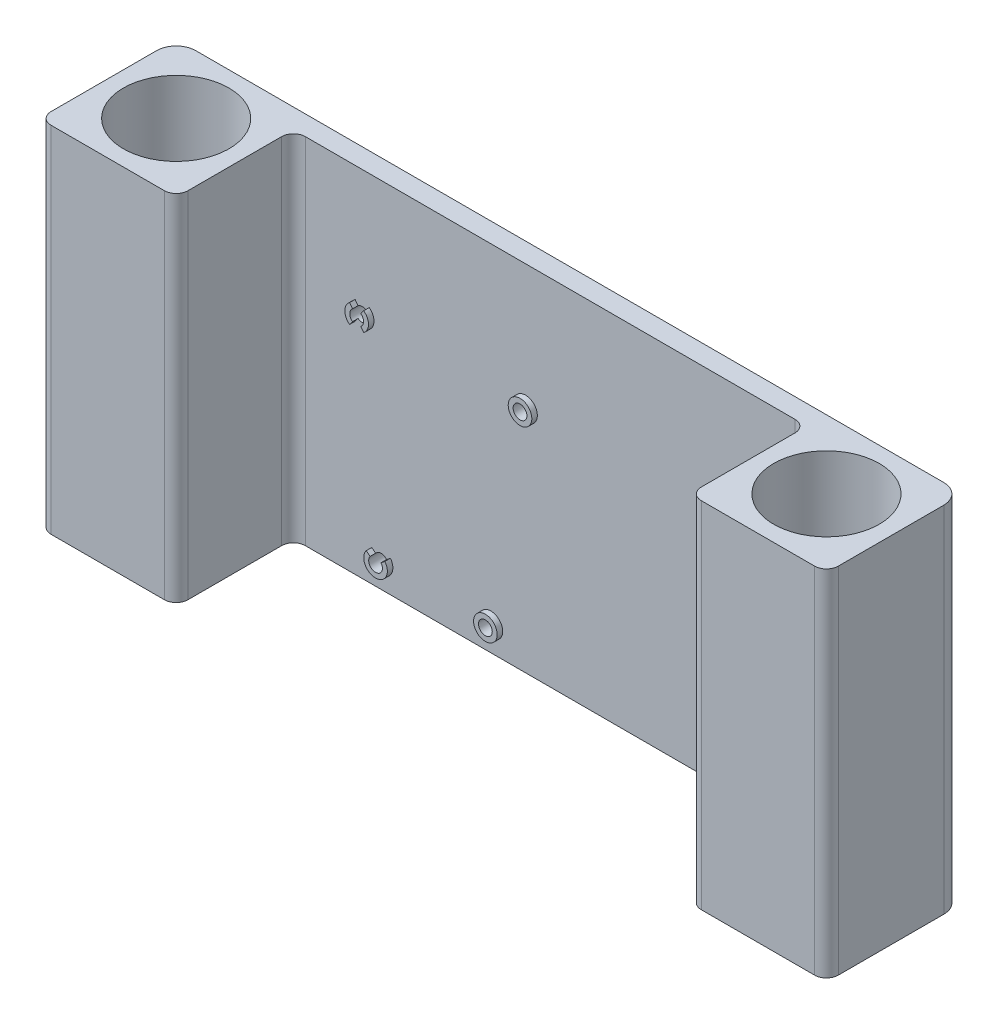
SolidWorks part; units mm, degrees
ref_plane "Front Plane" through (0, 0, 0) normal (0, 0, 1) x (1, 0, 0)
ref_plane "Top Plane" through (0, 0, 0) normal (0, 1, 0) x (1, 0, 0)
ref_plane "Right Plane" through (0, 0, 0) normal (1, 0, 0) x (0, 0, -1)
sketch "Sketch1" plane through (0, 0, 0) normal (0, 1, 0) x (1, 0, 0)
  line L1 (-17.4, 17.4) -> (17.4, 17.4)
  line L2 (-17.4, 17.4) -> (-17.4, -17.4)
  line L3 (-17.4, -17.4) -> (17.4, -17.4)
  line L4 (17.4, 12.4) -> (17.4, -17.4)
  line L5 (-17.4, 17.4) -> (17.4, -17.4) construction
  line L6 (-17.4, -17.4) -> (17.4, 17.4) construction
  line L11 (17.4, 17.4) -> (82.6, 17.4)
  line L13 (17.4, 12.4) -> (82.6, 12.4)
  line L14 (82.6, 17.4) -> (82.6, 12.4)
  circle A0 centre (0, 0) radius 13.4
  dimension "D1" = 26.8
  dimension "D2" = 34.8
  dimension "D3" = 34.8
  dimension "D4" = 5
extrude "Boss-Extrude1" add sketch "Sketch1" along normal blind 90 contours L14 L11 L4 L13 | L4 L1 L2 L3 A0 region at (16.7534, 0, -4.9925)
mirror "Mirror3" about plane through (82.6, 90, 0) normal (1, 0, 0) of "Boss-Extrude1"
fillet "Fillet1" radius 5 2 edges at (182.6, 45, -17.4) (-17.4, 45, -17.4)
fillet "Fillet2" radius 3 4 edges at (182.6, 45, 17.4) (147.8, 45, 17.4) (17.4, 45, 17.4) (-17.4, 45, 17.4)
fillet "Fillet3" radius 3 2 edges at (17.4, 45, -12.4) (147.8, 45, -12.4)
sketch "Sketch2" plane through (0, 0, -12.4) normal (0, 0, 1) x (1, 0, 0)
  line L1 (32.4, 4.7638) -> (32.4, 77.8661) construction
  line L3 (17.4, 0) -> (17.4, 90) construction
  circle A0 centre (39.65, 6.1978) radius 1.75
  circle A1 centre (67.55, 6.1978) radius 1.75
  circle A2 centre (34.85, 58.0978) radius 1.75
  circle A3 centre (76.35, 58.0978) radius 1.75
  point P8 (0, 0)
  point P9 (0, 0)
  point P10 (64.7447, 4.5183)
  point P11 (64.6447, 5.6176)
  point P12 (36.7447, 3.3545)
  point P13 (36.7447, 5.9964)
  point P14 (36.7447, 6.1978)
  dimension "D1" = 3.5
  dimension "D2" = 3.5
  dimension "D3" = 2.45
  dimension "D4" = 3.5
  dimension "D5" = 27.9
  dimension "D6" = 41.5
  dimension "D7" = 7.25
  dimension "D8" = 51.9
  dimension "D9" = 15
extrude "Cut-Extrude1" cut sketch "Sketch2" against normal blind 10
sketch "Sketch3" plane through (0, 0, -17.4) normal (0, 0, 1) x (1, 0, 0)
  line L13 (42.9409, 6.1978) -> (41.2954, 9.0478)
  line L14 (41.2954, 9.0478) -> (38.0046, 9.0478)
  line L15 (38.0046, 9.0478) -> (36.3591, 6.1978)
  line L16 (36.3591, 6.1978) -> (38.0046, 3.3478)
  line L17 (38.0046, 3.3478) -> (41.2954, 3.3478)
  line L18 (41.2954, 3.3478) -> (42.9409, 6.1978)
  line L19 (70.8409, 6.1978) -> (69.1954, 9.0478)
  line L20 (69.1954, 9.0478) -> (65.9046, 9.0478)
  line L21 (65.9046, 9.0478) -> (64.2591, 6.1978)
  line L22 (64.2591, 6.1978) -> (65.9046, 3.3478)
  line L23 (65.9046, 3.3478) -> (69.1954, 3.3478)
  line L24 (69.1954, 3.3478) -> (70.8409, 6.1978)
  line L25 (79.6409, 58.0978) -> (77.9954, 60.9478)
  line L26 (77.9954, 60.9478) -> (74.7046, 60.9478)
  line L27 (74.7046, 60.9478) -> (73.0591, 58.0978)
  line L28 (73.0591, 58.0978) -> (74.7046, 55.2478)
  line L29 (74.7046, 55.2478) -> (77.9954, 55.2478)
  line L30 (77.9954, 55.2478) -> (79.6409, 58.0978)
  line L31 (38.1409, 58.0978) -> (36.4954, 60.9478)
  line L32 (36.4954, 60.9478) -> (33.2046, 60.9478)
  line L33 (33.2046, 60.9478) -> (31.5591, 58.0978)
  line L34 (31.5591, 58.0978) -> (33.2046, 55.2478)
  line L35 (33.2046, 55.2478) -> (36.4954, 55.2478)
  line L36 (36.4954, 55.2478) -> (38.1409, 58.0978)
  circle A0 centre (39.65, 6.1978) radius 2.85 construction
  circle A1 centre (67.55, 6.1978) radius 2.85 construction
  circle A2 centre (76.35, 58.0978) radius 2.85 construction
  circle A3 centre (34.85, 58.0978) radius 2.85 construction
  dimension "D2" = 5.7
  dimension "D3" = 5.7
  dimension "D4" = 5.7
  dimension "D5" = 5.7
extrude "Cut-Extrude3" cut sketch "Sketch3" along normal blind 2.5
sketch "Sketch5" plane through (0, 0, -12.4) normal (0, 0, 1) x (1, 0, 0)
  line L0 (36.6417, 55.6916) -> (35.8951, 56.6942)
  line L1 (33.8049, 56.6942) -> (33.0583, 55.6916)
  line L2 (35.8951, 59.5014) -> (36.6417, 60.504)
  line L3 (33.8049, 59.5014) -> (33.0583, 60.504)
  line L4 (38.2668, 7.2698) -> (37.2788, 8.0356)
  line L5 (41.0332, 7.2698) -> (42.0212, 8.0356)
  circle A0 centre (67.55, 6.1978) radius 3
  arc A1 (37.2788, 8.0356) -> (42.0212, 8.0356) centre (39.65, 6.1978) ccw
  arc A2 (36.6417, 55.6916) -> (36.6417, 60.504) centre (34.85, 58.0978) ccw
  circle A3 centre (76.35, 58.0978) radius 3
  circle A4 centre (76.35, 58.0978) radius 1.75 construction
  circle A5 centre (34.85, 58.0978) radius 1.75 construction
  circle A6 centre (39.65, 6.1978) radius 1.75 construction
  circle A7 centre (67.55, 6.1978) radius 1.75 construction
  circle A8 centre (76.35, 58.0978) radius 1.75
  arc A9 (33.8049, 59.5014) -> (33.8049, 56.6942) centre (34.85, 58.0978) ccw
  arc A10 (38.2668, 7.2698) -> (41.0332, 7.2698) centre (39.65, 6.1978) ccw
  circle A11 centre (67.55, 6.1978) radius 1.75
  arc A12 (33.0583, 60.504) -> (33.0583, 55.6916) centre (34.85, 58.0978) ccw
  arc A13 (35.8951, 56.6942) -> (35.8951, 59.5014) centre (34.85, 58.0978) ccw
  dimension "D1" = 6
  dimension "D2" = 6
  dimension "D3" = 6
  dimension "D4" = 6
extrude "Boss-Extrude3" add sketch "Sketch5" along normal blind 1.4
